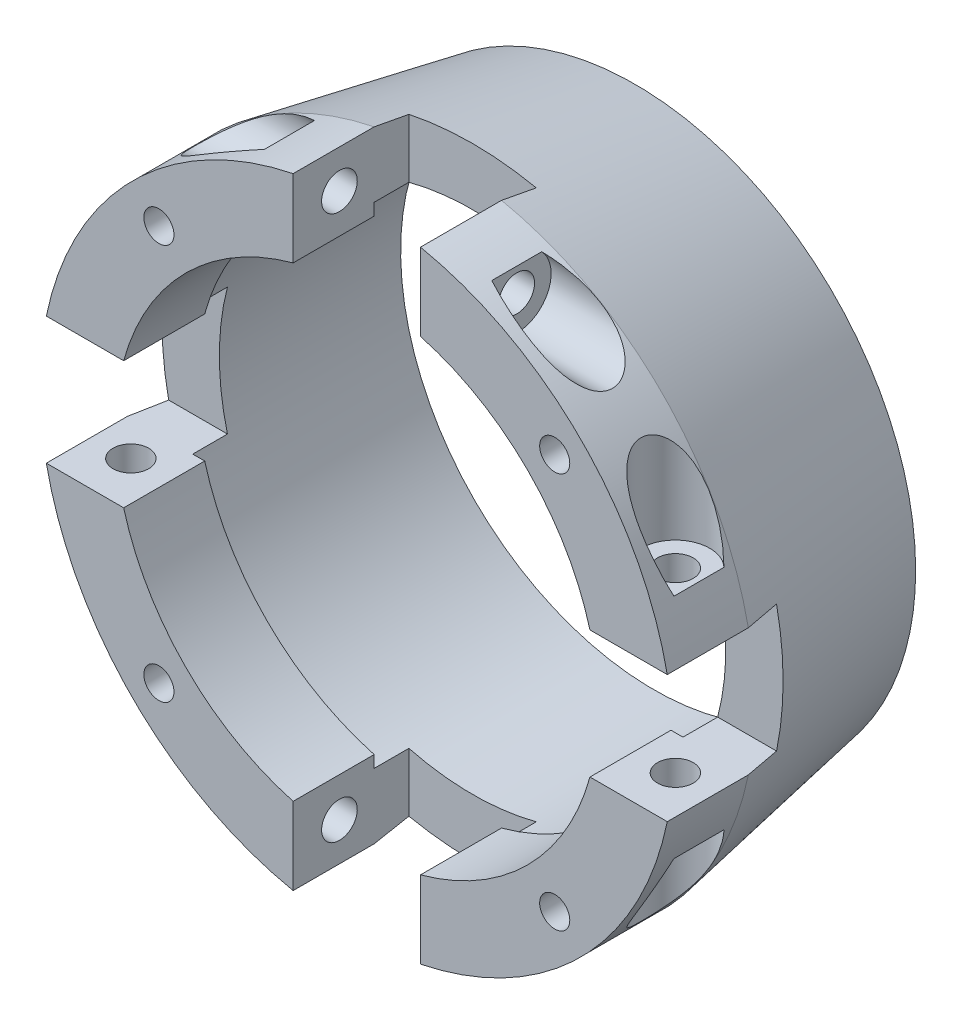
SolidWorks part; units mm, degrees
ref_plane "Front Plane" through (0, 0, 0) normal (1, 0, 0) x (0, 1, 0)
ref_plane "Top Plane" through (0, 0, 0) normal (0, 0, 1) x (0, 1, 0)
ref_plane "Right Plane" through (0, 0, 0) normal (0, 1, 0) x (-1, 0, 0)
sketch "Sketch1" plane through (0, 0, 0) normal (1, 0, 0) x (0, 1, 0)
  line L0 (0, 0) -> (27.7812, 0) construction
  line L1 (0, 0) -> (0, 33.02) construction
  line L2 (27.7812, 0) -> (27.7812, 24.13)
  line L3 (27.7812, 24.13) -> (26.5113, 24.13)
  line L4 (26.5113, 24.13) -> (26.5113, 33.02)
  line L8 (0, 33.02) -> (26.5113, 33.02) construction
  line L11 (27.7812, 0) -> (30.3213, 0)
  line L13 (34.7662, 33.02) -> (26.5113, 33.02)
  line L15 (34.7662, 33.02) -> (34.7662, 24.13)
  line L16 (34.7662, 24.13) -> (30.3213, 0)
  line L17 (27.7812, 24.13) -> (34.7662, 24.13) construction
  dimension "D1" = 27.7812
  dimension "D2" = 24.13
  dimension "D3" = 8.89
  dimension "D4" = 1.27
  dimension "D5" = 8.255
  dimension "D6" = 2.54
  dimension "D7" = 34.7662
revolve "base_ring" add sketch "Sketch1" angle 360 about L1
sketch "Sketch5" plane through (0, 0, 33.02) normal (0, 0, 1) x (1, 0, 0)
  line L0 (0, 0) -> (0, 25.5745) construction
  line L1 (-6.985, 38.2745) -> (6.985, 38.2745)
  line L2 (-6.985, 38.2745) -> (-6.985, 25.5745)
  line L3 (-6.985, 25.5745) -> (6.985, 25.5745)
  line L4 (6.985, 38.2745) -> (6.985, 25.5745)
  circle A0 centre (0, 0) radius 26.5113 construction
  dimension "D1" = 13.97
  dimension "D2" = 12.7
extrude "pulley_recess" cut sketch "Sketch5" against normal blind 12.7 and the other way through all
ref_plane "Plane1" through (34.7662, 0, 0) normal (1, 0, 0) x (0, 0, -1)
sketch "Sketch7" plane through (34.7662, 0, 0) normal (1, 0, 0) x (0, 0, -1)
  line L6 (-27.94, 29.8663) -> (-27.94, 34.0573) construction
  line L7 (-24.13, 34.0573) -> (-33.02, 34.0573) construction
  line L9 (-24.13, 34.0573) -> (-24.13, -34.7662) construction
  point P0 (-27.94, 29.8663)
  dimension "D1" = 3.81
  dimension "D2" = 4.191
hole_wizard "pulley_bolt_hole" positions "Sketch7" profile "Sketch8" counterbore size "#5" standard "ANSI Inch"
sketch "Sketch8" plane through (34.7662, 29.8663, 27.94) normal (0, 1, 0) x (0, 0, -1)
  line L0 (0, 0) -> (0, 39.2752)
  line L1 (0, 39.2752) -> (1.9558, 38.1)
  line L2 (1.9558, 38.1) -> (1.9558, 22.3012)
  line L3 (1.9558, 22.3012) -> (3.7706, 22.3012)
  line L4 (3.7706, 22.3012) -> (3.7706, 0)
  line L5 (3.7706, 0) -> (0, 0)
  line L10 (0, 39.2752) -> (-1.9558, 38.1) construction
  line L11 (0, -6.35) -> (0, 107.95) construction
  dimension "Hole Dia." = 3.9116
  dimension "Hole Depth" = 38.1
  dimension "C'Bore Dia." = 7.5413
  dimension "C'Bore Depth" = 22.3012
  dimension "Drill Angle" = 118
mirror "bolthole_mirror" about plane through (0, 0, 0) normal (1, 0, 0) of "pulley_bolt_hole"
sketch "Sketch11" plane through (0, 0, 33.02) normal (0, 0, 1) x (1, 0, 0)
  line L0 (0, 0) -> (24.5835, 24.5835) construction
  line L3 (0, 0) -> (0, 34.0644) construction
  circle A0 centre (21.7098, 21.7098) radius 1.651
  arc A3 (6.985, 33.3406) -> (-6.985, 33.3406) centre (0, 0) ccw construction
  arc A4 (-6.985, 34.0573) -> (6.985, 34.0573) centre (0, 0) ccw construction
  point P2 (15.6872, 27.0201)
  dimension "D1" = 3.302
  dimension "D2" = 4.064
  dimension "D3" = 45
extrude "nosecone_pin_hole" cut sketch "Sketch11" against normal blind 10.16
pattern_circular "CirPattern1" count 4 over 360 about axis through (0, 0, 0) along (0, 0, -1) of "pulley_recess", "pulley_bolt_hole", "bolthole_mirror", "nosecone_pin_hole"
chamfer "Chamfer1" distance 2.54 angle 45 1 edges at (-30.3213, 0, 0) first distance on face at (-30.3213, 0, 0)
